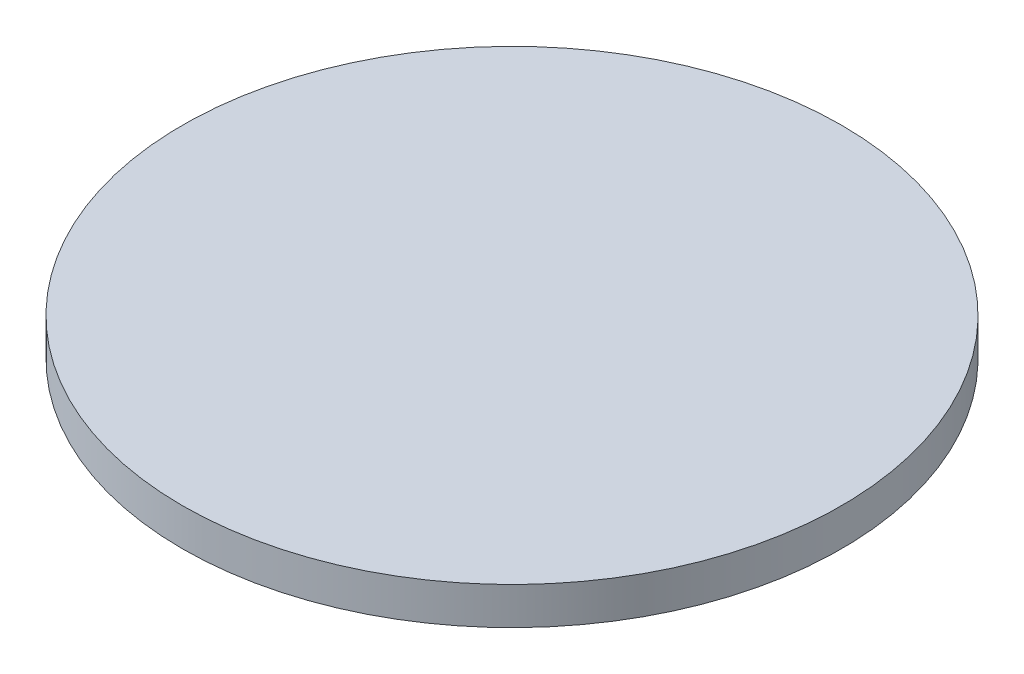
SolidWorks part; units mm, degrees
material "1060 Alloy"
ref_plane "Front Plane" through (0, 0, 0) normal (0, 0, 1) x (1, 0, 0)
ref_plane "Top Plane" through (0, 0, 0) normal (0, 1, 0) x (1, 0, 0)
ref_plane "Right Plane" through (0, 0, 0) normal (1, 0, 0) x (0, 0, -1)
sketch "Sketch1" plane through (0, 0, 0) normal (0, 1, 0) x (1, 0, 0)
  circle A0 centre (0, 0) radius 15.875
  dimension "D1" = 31.75
extrude "Boss-Extrude1" add sketch "Sketch1" along normal blind 1
sketch "Sketch2" plane through (0, 0, 0) normal (0, -1, 0) x (1, 0, 0)
  circle A0 centre (0, 0) radius 15.875
  circle A1 centre (0, 0) radius 9.525
  circle A2 centre (0, 0) radius 15.875 construction
  dimension "D1" = 0
  dimension "D2" = 19.05
extrude "Boss-Extrude2" add sketch "Sketch2" along normal blind 0.8
thread "Thread1" pitch 0.25 method cut profile "Thread Profile1" start angle 0, offset 0, length 1, pitch 0.25, diameter 19.05
ref_plane "Plane1" through (9.525, -0.8, 0) normal (0, 0, 1) x (1, 0, 0)
sketch "Thread Profile1" plane through (9.525, -0.8, 0) normal (0, 0, 1) x (1, 0, 0)
  line L0 (0, 0) -> (0, 0.25) construction
  line L1 (0, 0) -> (0.1353, 0.0781)
  line L2 (0.1353, 0.0781) -> (0.1353, 0.1094)
  line L3 (0.1353, 0.1094) -> (0, 0.1875)
  line L4 (0.1353, 0.0937) -> (0, 0.0937) construction
  line L11 (0, 0) -> (0, 0.1875)
  point P2 (0, 0)
  dimension "Pitch" = 0.25
  dimension "Profile_Angle" = 60
  dimension "Profile_Land" = 0.0312
  dimension "Profile_Height" = 0.1353
